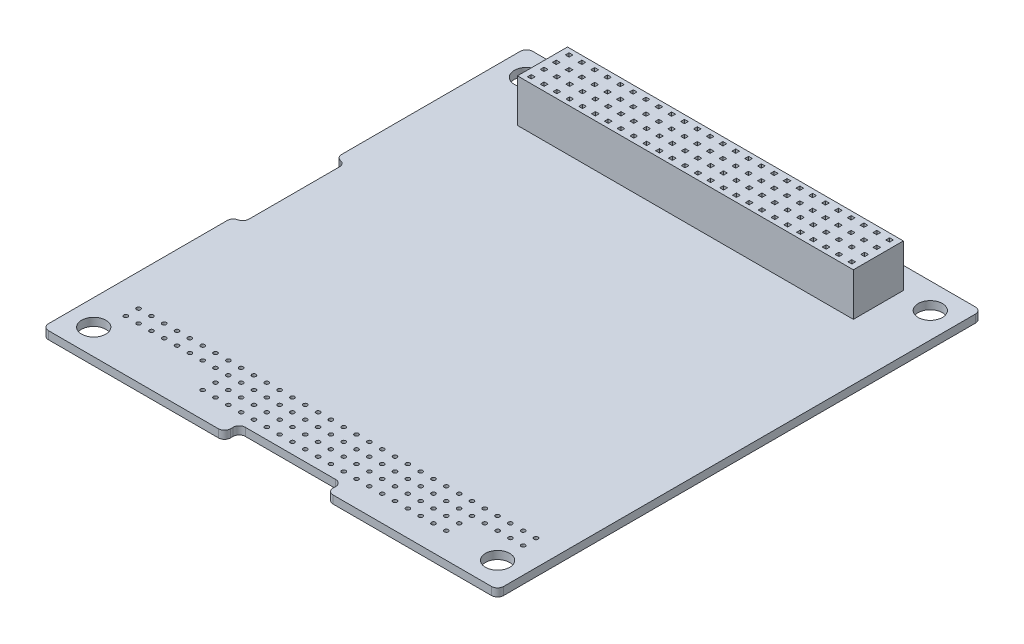
SolidWorks part; units mm, degrees
ref_plane "Front Plane" through (0, 0, 0) normal (0, 0, 1) x (1, 0, 0)
ref_plane "Top Plane" through (0, 0, 0) normal (0, 1, 0) x (1, 0, 0)
ref_plane "Right Plane" through (0, 0, 0) normal (1, 0, 0) x (0, 0, -1)
sketch "Sketch1" plane through (0, 0, 0) normal (0, 1, 0) x (1, 0, 0)
  line L1 (-45.085, -47.945) -> (45.085, -47.945)
  line L2 (-45.085, -47.945) -> (-45.085, 47.945)
  line L3 (-45.085, 47.945) -> (45.085, 47.945)
  line L4 (45.085, -47.945) -> (45.085, 47.945)
  line L5 (-45.085, -47.945) -> (45.085, 47.945) construction
  line L6 (-45.085, 47.945) -> (45.085, -47.945) construction
  point P0 (0, 0)
  dimension "D1" = 95.89
  dimension "D2" = 90.17
extrude "Boss-Extrude1" add sketch "Sketch1" along normal blind 1.57
sketch "Sketch2" plane through (0, 1.57, 0) normal (0, 1, 0) x (1, 0, 0)
  line L0 (-45.085, 47.945) -> (-9.015, 47.945) construction
  line L1 (45.085, 47.945) -> (-45.085, 47.945) construction
  line L2 (-45.085, -47.945) -> (-45.085, -10.135) construction
  line L3 (-9.015, 47.945) -> (11.305, 47.945)
  line L4 (-9.015, 47.945) -> (-9.015, 45.015)
  line L5 (-9.015, 45.015) -> (11.305, 45.015)
  line L6 (11.305, 47.945) -> (11.305, 45.015)
  line L7 (-45.085, 47.945) -> (-45.085, -47.945) construction
  line L8 (-45.085, -47.945) -> (-9.015, -47.945) construction
  line L9 (-45.085, -10.135) -> (-43.165, -10.135)
  line L10 (-45.085, -10.135) -> (-45.085, 10.135)
  line L11 (-45.085, 10.135) -> (-43.165, 10.135)
  line L12 (-43.165, -10.135) -> (-43.165, 10.135)
  line L13 (-45.085, -47.945) -> (45.085, -47.945) construction
  line L15 (-9.015, -47.945) -> (11.305, -47.945)
  line L16 (-9.015, -47.945) -> (-9.015, -45.025)
  line L17 (-9.015, -45.025) -> (11.305, -45.025)
  line L18 (11.305, -47.945) -> (11.305, -45.025)
  dimension "D1" = 36.07
  dimension "D2" = 20.32
  dimension "D3" = 2.93
  dimension "D4" = 37.81
  dimension "D5" = 20.27
  dimension "D6" = 1.92
  dimension "D7" = 2.92
extrude "Cut-Extrude1" cut sketch "Sketch2" against normal blind 1.57
sketch "Sketch3" plane through (0, 1.57, 0) normal (0, 1, 0) x (1, 0, 0)
  line L0 (-45.085, -47.945) -> (-40.005, -47.945) construction
  line L1 (-45.085, -47.945) -> (-9.015, -47.945) construction
  line L2 (-40.005, -47.945) -> (-40.005, -42.865) construction
  line L3 (45.085, -47.945) -> (40.005, -47.945) construction
  line L4 (11.305, -47.945) -> (45.085, -47.945) construction
  line L5 (40.005, -47.945) -> (40.005, -42.865) construction
  line L6 (-45.085, 47.945) -> (-40.005, 47.945) construction
  line L7 (-9.015, 47.945) -> (-45.085, 47.945) construction
  line L8 (-40.005, 47.945) -> (-40.005, 42.865) construction
  circle A0 centre (-40.005, -42.865) radius 2.4
  circle A1 centre (40.005, -42.865) radius 2.4
  circle A2 centre (-40.005, 42.865) radius 2.4
  circle A3 centre (40.005, 42.865) radius 2.4
  dimension "D3" = 4.8
  dimension "D6" = 5.08
  dimension "D4" = 5.08
  dimension "D5" = 4.8
  dimension "D7" = 4.8
  dimension "D8" = 4.8
  dimension "D1" = 5.08
  dimension "D2" = 5.08
extrude "Cut-Extrude2" cut sketch "Sketch3" against normal blind 1.57
sketch "Sketch4" plane through (0, 1.57, 0) normal (0, 1, 0) x (1, 0, 0)
  line L0 (-45.085, 47.945) -> (-45.085, 35.245) construction
  line L1 (-45.085, 47.945) -> (-45.085, 10.135) construction
  line L2 (-45.085, 35.245) -> (-31.115, 35.245) construction
  line L3 (-31.115, 35.245) -> (-32.639, 35.245)
  line L4 (-32.639, 35.245) -> (-32.639, 33.721) construction
  line L6 (-32.639, 33.721) -> (33.909, 33.721)
  line L7 (-32.639, 33.721) -> (-32.639, 43.627)
  line L8 (-32.639, 43.627) -> (33.909, 43.627)
  line L9 (33.909, 33.721) -> (33.909, 43.627)
  dimension "D1" = 12.7
  dimension "D2" = 13.97
  dimension "D3" = 1.524
  dimension "D4" = 1.524
  dimension "D5" = 9.906
  dimension "D6" = 66.548
extrude "Boss-Extrude3" add sketch "Sketch4" along normal blind 8.509 contours L6 L9 L8 L7 region at (0.635, 1.57, -38.674)
fillet "Fillet7" radius 1.2 1 edges at (-9.015, 0.785, 45.025)
fillet "Fillet8" radius 1.2 1 edges at (-9.015, 0.785, 47.945)
fillet "Fillet9" radius 1.2 2 edges at (11.305, 0.785, 47.945) (11.305, 0.785, 45.025)
fillet "Fillet10" radius 1.2 1 edges at (45.085, 0.785, 47.945)
fillet "Fillet11" radius 1.2 1 edges at (45.085, 0.785, -47.945)
fillet "Fillet12" radius 1.2 2 edges at (11.305, 0.785, -45.015) (11.305, 0.785, -47.945)
fillet "Fillet13" radius 1.2 2 edges at (-9.015, 0.785, -47.945) (-9.015, 0.785, -45.015)
fillet "Fillet14" radius 1.2 1 edges at (-45.085, 0.785, -47.945)
fillet "Fillet17" radius 1.2 1 edges at (-45.085, 0.785, -10.135)
fillet "Fillet18" radius 1.2 1 edges at (-43.165, 0.785, -10.135)
fillet "Fillet19" radius 1.2 1 edges at (-45.085, 0.785, 10.135)
fillet "Fillet20" radius 1.2 1 edges at (-43.165, 0.785, 10.135)
fillet "Fillet21" radius 1.2 1 edges at (-45.085, 0.785, 47.945)
sketch "Sketch7" plane through (0, 10.079, 0) normal (0, 1, 0) x (1, 0, 0)
  line L0 (-32.639, 33.721) -> (-31.115, 33.721) construction
  line L1 (-32.639, 33.721) -> (33.909, 33.721) construction
  line L2 (-31.115, 33.721) -> (-31.115, 34.9275) construction
  line L3 (-28.956, 34.5465) -> (-28.194, 34.5465)
  line L4 (-31.496, 34.5465) -> (-30.734, 34.5465)
  line L5 (-31.496, 34.5465) -> (-31.496, 35.3085)
  line L6 (-31.496, 35.3085) -> (-30.734, 35.3085)
  line L7 (-30.734, 34.5465) -> (-30.734, 35.3085)
  line L8 (-31.496, 34.5465) -> (-30.734, 35.3085) construction
  line L9 (-31.496, 35.3085) -> (-30.734, 34.5465) construction
  line L10 (-28.194, 34.5465) -> (-28.194, 35.3085)
  line L11 (-28.956, 35.3085) -> (-28.194, 35.3085)
  line L12 (-28.956, 34.5465) -> (-28.956, 35.3085)
  line L13 (-26.416, 34.5465) -> (-25.654, 34.5465)
  line L14 (-25.654, 34.5465) -> (-25.654, 35.3085)
  line L15 (-26.416, 35.3085) -> (-25.654, 35.3085)
  line L16 (-26.416, 34.5465) -> (-26.416, 35.3085)
  line L17 (-23.876, 34.5465) -> (-23.114, 34.5465)
  line L18 (-23.114, 34.5465) -> (-23.114, 35.3085)
  line L19 (-23.876, 35.3085) -> (-23.114, 35.3085)
  line L20 (-23.876, 34.5465) -> (-23.876, 35.3085)
  line L21 (-21.336, 34.5465) -> (-20.574, 34.5465)
  line L22 (-20.574, 34.5465) -> (-20.574, 35.3085)
  line L23 (-21.336, 35.3085) -> (-20.574, 35.3085)
  line L24 (-21.336, 34.5465) -> (-21.336, 35.3085)
  line L25 (-18.796, 34.5465) -> (-18.034, 34.5465)
  line L26 (-18.034, 34.5465) -> (-18.034, 35.3085)
  line L27 (-18.796, 35.3085) -> (-18.034, 35.3085)
  line L28 (-18.796, 34.5465) -> (-18.796, 35.3085)
  line L29 (-16.256, 34.5465) -> (-15.494, 34.5465)
  line L30 (-15.494, 34.5465) -> (-15.494, 35.3085)
  line L31 (-16.256, 35.3085) -> (-15.494, 35.3085)
  line L32 (-16.256, 34.5465) -> (-16.256, 35.3085)
  line L33 (-13.716, 34.5465) -> (-12.954, 34.5465)
  line L34 (-12.954, 34.5465) -> (-12.954, 35.3085)
  line L35 (-13.716, 35.3085) -> (-12.954, 35.3085)
  line L36 (-13.716, 34.5465) -> (-13.716, 35.3085)
  line L37 (-11.176, 34.5465) -> (-10.414, 34.5465)
  line L38 (-10.414, 34.5465) -> (-10.414, 35.3085)
  line L39 (-11.176, 35.3085) -> (-10.414, 35.3085)
  line L40 (-11.176, 34.5465) -> (-11.176, 35.3085)
  line L41 (-8.636, 34.5465) -> (-7.874, 34.5465)
  line L42 (-7.874, 34.5465) -> (-7.874, 35.3085)
  line L43 (-8.636, 35.3085) -> (-7.874, 35.3085)
  line L44 (-8.636, 34.5465) -> (-8.636, 35.3085)
  line L45 (-6.096, 34.5465) -> (-5.334, 34.5465)
  line L46 (-5.334, 34.5465) -> (-5.334, 35.3085)
  line L47 (-6.096, 35.3085) -> (-5.334, 35.3085)
  line L48 (-6.096, 34.5465) -> (-6.096, 35.3085)
  line L49 (-3.556, 34.5465) -> (-2.794, 34.5465)
  line L50 (-2.794, 34.5465) -> (-2.794, 35.3085)
  line L51 (-3.556, 35.3085) -> (-2.794, 35.3085)
  line L52 (-3.556, 34.5465) -> (-3.556, 35.3085)
  line L53 (-1.016, 34.5465) -> (-0.254, 34.5465)
  line L54 (-0.254, 34.5465) -> (-0.254, 35.3085)
  line L55 (-1.016, 35.3085) -> (-0.254, 35.3085)
  line L56 (-1.016, 34.5465) -> (-1.016, 35.3085)
  line L57 (1.524, 34.5465) -> (2.286, 34.5465)
  line L58 (2.286, 34.5465) -> (2.286, 35.3085)
  line L59 (1.524, 35.3085) -> (2.286, 35.3085)
  line L60 (1.524, 34.5465) -> (1.524, 35.3085)
  line L61 (4.064, 34.5465) -> (4.826, 34.5465)
  line L62 (4.826, 34.5465) -> (4.826, 35.3085)
  line L63 (4.064, 35.3085) -> (4.826, 35.3085)
  line L64 (4.064, 34.5465) -> (4.064, 35.3085)
  line L65 (6.604, 34.5465) -> (7.366, 34.5465)
  line L66 (7.366, 34.5465) -> (7.366, 35.3085)
  line L67 (6.604, 35.3085) -> (7.366, 35.3085)
  line L68 (6.604, 34.5465) -> (6.604, 35.3085)
  line L69 (9.144, 34.5465) -> (9.906, 34.5465)
  line L70 (9.906, 34.5465) -> (9.906, 35.3085)
  line L71 (9.144, 35.3085) -> (9.906, 35.3085)
  line L72 (9.144, 34.5465) -> (9.144, 35.3085)
  line L73 (11.684, 34.5465) -> (12.446, 34.5465)
  line L74 (12.446, 34.5465) -> (12.446, 35.3085)
  line L75 (11.684, 35.3085) -> (12.446, 35.3085)
  line L76 (11.684, 34.5465) -> (11.684, 35.3085)
  line L77 (14.224, 34.5465) -> (14.986, 34.5465)
  line L78 (14.986, 34.5465) -> (14.986, 35.3085)
  line L79 (14.224, 35.3085) -> (14.986, 35.3085)
  line L80 (14.224, 34.5465) -> (14.224, 35.3085)
  line L81 (16.764, 34.5465) -> (17.526, 34.5465)
  line L82 (17.526, 34.5465) -> (17.526, 35.3085)
  line L83 (16.764, 35.3085) -> (17.526, 35.3085)
  line L84 (16.764, 34.5465) -> (16.764, 35.3085)
  line L85 (19.304, 34.5465) -> (20.066, 34.5465)
  line L86 (20.066, 34.5465) -> (20.066, 35.3085)
  line L87 (19.304, 35.3085) -> (20.066, 35.3085)
  line L88 (19.304, 34.5465) -> (19.304, 35.3085)
  line L89 (21.844, 34.5465) -> (22.606, 34.5465)
  line L90 (22.606, 34.5465) -> (22.606, 35.3085)
  line L91 (21.844, 35.3085) -> (22.606, 35.3085)
  line L92 (21.844, 34.5465) -> (21.844, 35.3085)
  line L93 (24.384, 34.5465) -> (25.146, 34.5465)
  line L94 (25.146, 34.5465) -> (25.146, 35.3085)
  line L95 (24.384, 35.3085) -> (25.146, 35.3085)
  line L96 (24.384, 34.5465) -> (24.384, 35.3085)
  line L97 (26.924, 34.5465) -> (27.686, 34.5465)
  line L98 (27.686, 34.5465) -> (27.686, 35.3085)
  line L99 (26.924, 35.3085) -> (27.686, 35.3085)
  line L100 (26.924, 34.5465) -> (26.924, 35.3085)
  line L101 (29.464, 34.5465) -> (30.226, 34.5465)
  line L102 (30.226, 34.5465) -> (30.226, 35.3085)
  line L103 (29.464, 35.3085) -> (30.226, 35.3085)
  line L104 (29.464, 34.5465) -> (29.464, 35.3085)
  line L105 (32.004, 34.5465) -> (32.766, 34.5465)
  line L106 (32.766, 34.5465) -> (32.766, 35.3085)
  line L107 (32.004, 35.3085) -> (32.766, 35.3085)
  line L108 (32.004, 34.5465) -> (32.004, 35.3085)
  dimension "D1" = 1.524
  dimension "D2" = 1.2065
  dimension "D3" = 0.762
  dimension "D4" = 0.762
  dimension "D5" = 26
extrude "Cut-Extrude4" cut sketch "Sketch7" against normal blind 8.509
sketch "Sketch8" plane through (0, 10.079, 0) normal (0, 1, 0) x (1, 0, 0)
  line L0 (-31.496, 35.3085) -> (-30.734, 34.5465) construction
  line L1 (-31.496, 34.5465) -> (-30.734, 35.3085) construction
  line L2 (-31.115, 34.9275) -> (-31.115, 37.4675) construction
  line L3 (-28.194, 37.0865) -> (-28.956, 37.0865)
  line L4 (-30.734, 37.8485) -> (-31.496, 37.8485)
  line L5 (-30.734, 37.8485) -> (-30.734, 37.0865)
  line L6 (-30.734, 37.0865) -> (-31.496, 37.0865)
  line L7 (-31.496, 37.8485) -> (-31.496, 37.0865)
  line L8 (-30.734, 37.8485) -> (-31.496, 37.0865) construction
  line L9 (-30.734, 37.0865) -> (-31.496, 37.8485) construction
  line L10 (-28.956, 37.8485) -> (-28.956, 37.0865)
  line L11 (-28.194, 37.8485) -> (-28.956, 37.8485)
  line L12 (-28.194, 37.8485) -> (-28.194, 37.0865)
  line L13 (-25.654, 37.0865) -> (-26.416, 37.0865)
  line L14 (-26.416, 37.8485) -> (-26.416, 37.0865)
  line L15 (-25.654, 37.8485) -> (-26.416, 37.8485)
  line L16 (-25.654, 37.8485) -> (-25.654, 37.0865)
  line L17 (-23.114, 37.0865) -> (-23.876, 37.0865)
  line L18 (-23.876, 37.8485) -> (-23.876, 37.0865)
  line L19 (-23.114, 37.8485) -> (-23.876, 37.8485)
  line L20 (-23.114, 37.8485) -> (-23.114, 37.0865)
  line L21 (-20.574, 37.0865) -> (-21.336, 37.0865)
  line L22 (-21.336, 37.8485) -> (-21.336, 37.0865)
  line L23 (-20.574, 37.8485) -> (-21.336, 37.8485)
  line L24 (-20.574, 37.8485) -> (-20.574, 37.0865)
  line L25 (-18.034, 37.0865) -> (-18.796, 37.0865)
  line L26 (-18.796, 37.8485) -> (-18.796, 37.0865)
  line L27 (-18.034, 37.8485) -> (-18.796, 37.8485)
  line L28 (-18.034, 37.8485) -> (-18.034, 37.0865)
  line L29 (-15.494, 37.0865) -> (-16.256, 37.0865)
  line L30 (-16.256, 37.8485) -> (-16.256, 37.0865)
  line L31 (-15.494, 37.8485) -> (-16.256, 37.8485)
  line L32 (-15.494, 37.8485) -> (-15.494, 37.0865)
  line L33 (-12.954, 37.0865) -> (-13.716, 37.0865)
  line L34 (-13.716, 37.8485) -> (-13.716, 37.0865)
  line L35 (-12.954, 37.8485) -> (-13.716, 37.8485)
  line L36 (-12.954, 37.8485) -> (-12.954, 37.0865)
  line L37 (-10.414, 37.0865) -> (-11.176, 37.0865)
  line L38 (-11.176, 37.8485) -> (-11.176, 37.0865)
  line L39 (-10.414, 37.8485) -> (-11.176, 37.8485)
  line L40 (-10.414, 37.8485) -> (-10.414, 37.0865)
  line L41 (-7.874, 37.0865) -> (-8.636, 37.0865)
  line L42 (-8.636, 37.8485) -> (-8.636, 37.0865)
  line L43 (-7.874, 37.8485) -> (-8.636, 37.8485)
  line L44 (-7.874, 37.8485) -> (-7.874, 37.0865)
  line L45 (-5.334, 37.0865) -> (-6.096, 37.0865)
  line L46 (-6.096, 37.8485) -> (-6.096, 37.0865)
  line L47 (-5.334, 37.8485) -> (-6.096, 37.8485)
  line L48 (-5.334, 37.8485) -> (-5.334, 37.0865)
  line L49 (-2.794, 37.0865) -> (-3.556, 37.0865)
  line L50 (-3.556, 37.8485) -> (-3.556, 37.0865)
  line L51 (-2.794, 37.8485) -> (-3.556, 37.8485)
  line L52 (-2.794, 37.8485) -> (-2.794, 37.0865)
  line L53 (-0.254, 37.0865) -> (-1.016, 37.0865)
  line L54 (-1.016, 37.8485) -> (-1.016, 37.0865)
  line L55 (-0.254, 37.8485) -> (-1.016, 37.8485)
  line L56 (-0.254, 37.8485) -> (-0.254, 37.0865)
  line L57 (2.286, 37.0865) -> (1.524, 37.0865)
  line L58 (1.524, 37.8485) -> (1.524, 37.0865)
  line L59 (2.286, 37.8485) -> (1.524, 37.8485)
  line L60 (2.286, 37.8485) -> (2.286, 37.0865)
  line L61 (4.826, 37.0865) -> (4.064, 37.0865)
  line L62 (4.064, 37.8485) -> (4.064, 37.0865)
  line L63 (4.826, 37.8485) -> (4.064, 37.8485)
  line L64 (4.826, 37.8485) -> (4.826, 37.0865)
  line L65 (7.366, 37.0865) -> (6.604, 37.0865)
  line L66 (6.604, 37.8485) -> (6.604, 37.0865)
  line L67 (7.366, 37.8485) -> (6.604, 37.8485)
  line L68 (7.366, 37.8485) -> (7.366, 37.0865)
  line L69 (9.906, 37.0865) -> (9.144, 37.0865)
  line L70 (9.144, 37.8485) -> (9.144, 37.0865)
  line L71 (9.906, 37.8485) -> (9.144, 37.8485)
  line L72 (9.906, 37.8485) -> (9.906, 37.0865)
  line L73 (12.446, 37.0865) -> (11.684, 37.0865)
  line L74 (11.684, 37.8485) -> (11.684, 37.0865)
  line L75 (12.446, 37.8485) -> (11.684, 37.8485)
  line L76 (12.446, 37.8485) -> (12.446, 37.0865)
  line L77 (14.986, 37.0865) -> (14.224, 37.0865)
  line L78 (14.224, 37.8485) -> (14.224, 37.0865)
  line L79 (14.986, 37.8485) -> (14.224, 37.8485)
  line L80 (14.986, 37.8485) -> (14.986, 37.0865)
  line L81 (17.526, 37.0865) -> (16.764, 37.0865)
  line L82 (16.764, 37.8485) -> (16.764, 37.0865)
  line L83 (17.526, 37.8485) -> (16.764, 37.8485)
  line L84 (17.526, 37.8485) -> (17.526, 37.0865)
  line L85 (20.066, 37.0865) -> (19.304, 37.0865)
  line L86 (19.304, 37.8485) -> (19.304, 37.0865)
  line L87 (20.066, 37.8485) -> (19.304, 37.8485)
  line L88 (20.066, 37.8485) -> (20.066, 37.0865)
  line L89 (22.606, 37.0865) -> (21.844, 37.0865)
  line L90 (21.844, 37.8485) -> (21.844, 37.0865)
  line L91 (22.606, 37.8485) -> (21.844, 37.8485)
  line L92 (22.606, 37.8485) -> (22.606, 37.0865)
  line L93 (25.146, 37.0865) -> (24.384, 37.0865)
  line L94 (24.384, 37.8485) -> (24.384, 37.0865)
  line L95 (25.146, 37.8485) -> (24.384, 37.8485)
  line L96 (25.146, 37.8485) -> (25.146, 37.0865)
  line L97 (27.686, 37.0865) -> (26.924, 37.0865)
  line L98 (26.924, 37.8485) -> (26.924, 37.0865)
  line L99 (27.686, 37.8485) -> (26.924, 37.8485)
  line L100 (27.686, 37.8485) -> (27.686, 37.0865)
  line L101 (30.226, 37.0865) -> (29.464, 37.0865)
  line L102 (29.464, 37.8485) -> (29.464, 37.0865)
  line L103 (30.226, 37.8485) -> (29.464, 37.8485)
  line L104 (30.226, 37.8485) -> (30.226, 37.0865)
  line L105 (32.766, 37.0865) -> (32.004, 37.0865)
  line L106 (32.004, 37.8485) -> (32.004, 37.0865)
  line L107 (32.766, 37.8485) -> (32.004, 37.8485)
  line L108 (32.766, 37.8485) -> (32.766, 37.0865)
  dimension "D1" = 2.54
  dimension "D2" = 0.762
  dimension "D3" = 26
extrude "Cut-Extrude5" cut sketch "Sketch8" against normal blind 8.509
sketch "Sketch9" plane through (0, 10.079, 0) normal (0, 1, 0) x (1, 0, 0)
  line L0 (-31.496, 37.0865) -> (-30.734, 37.8485) construction
  line L1 (-30.734, 37.8485) -> (-30.734, 37.0865) construction
  line L2 (-30.734, 37.0865) -> (-31.496, 37.8485) construction
  line L3 (-31.496, 37.8485) -> (-31.115, 37.4675) construction
  line L4 (-31.115, 37.4675) -> (-31.115, 39.8805) construction
  line L5 (-28.956, 39.4995) -> (-28.194, 39.4995)
  line L6 (-31.496, 39.4995) -> (-30.734, 39.4995)
  line L7 (-31.496, 39.4995) -> (-31.496, 40.2615)
  line L8 (-31.496, 40.2615) -> (-30.734, 40.2615)
  line L9 (-30.734, 39.4995) -> (-30.734, 40.2615)
  line L10 (-31.496, 39.4995) -> (-30.734, 40.2615) construction
  line L11 (-31.496, 40.2615) -> (-30.734, 39.4995) construction
  line L12 (-28.194, 39.4995) -> (-28.194, 40.2615)
  line L13 (-28.956, 40.2615) -> (-28.194, 40.2615)
  line L14 (-28.956, 39.4995) -> (-28.956, 40.2615)
  line L15 (-26.416, 39.4995) -> (-25.654, 39.4995)
  line L16 (-25.654, 39.4995) -> (-25.654, 40.2615)
  line L17 (-26.416, 40.2615) -> (-25.654, 40.2615)
  line L18 (-26.416, 39.4995) -> (-26.416, 40.2615)
  line L19 (-23.876, 39.4995) -> (-23.114, 39.4995)
  line L20 (-23.114, 39.4995) -> (-23.114, 40.2615)
  line L21 (-23.876, 40.2615) -> (-23.114, 40.2615)
  line L22 (-23.876, 39.4995) -> (-23.876, 40.2615)
  line L23 (-21.336, 39.4995) -> (-20.574, 39.4995)
  line L24 (-20.574, 39.4995) -> (-20.574, 40.2615)
  line L25 (-21.336, 40.2615) -> (-20.574, 40.2615)
  line L26 (-21.336, 39.4995) -> (-21.336, 40.2615)
  line L27 (-18.796, 39.4995) -> (-18.034, 39.4995)
  line L28 (-18.034, 39.4995) -> (-18.034, 40.2615)
  line L29 (-18.796, 40.2615) -> (-18.034, 40.2615)
  line L30 (-18.796, 39.4995) -> (-18.796, 40.2615)
  line L31 (-16.256, 39.4995) -> (-15.494, 39.4995)
  line L32 (-15.494, 39.4995) -> (-15.494, 40.2615)
  line L33 (-16.256, 40.2615) -> (-15.494, 40.2615)
  line L34 (-16.256, 39.4995) -> (-16.256, 40.2615)
  line L35 (-13.716, 39.4995) -> (-12.954, 39.4995)
  line L36 (-12.954, 39.4995) -> (-12.954, 40.2615)
  line L37 (-13.716, 40.2615) -> (-12.954, 40.2615)
  line L38 (-13.716, 39.4995) -> (-13.716, 40.2615)
  line L39 (-11.176, 39.4995) -> (-10.414, 39.4995)
  line L40 (-10.414, 39.4995) -> (-10.414, 40.2615)
  line L41 (-11.176, 40.2615) -> (-10.414, 40.2615)
  line L42 (-11.176, 39.4995) -> (-11.176, 40.2615)
  line L43 (-8.636, 39.4995) -> (-7.874, 39.4995)
  line L44 (-7.874, 39.4995) -> (-7.874, 40.2615)
  line L45 (-8.636, 40.2615) -> (-7.874, 40.2615)
  line L46 (-8.636, 39.4995) -> (-8.636, 40.2615)
  line L47 (-6.096, 39.4995) -> (-5.334, 39.4995)
  line L48 (-5.334, 39.4995) -> (-5.334, 40.2615)
  line L49 (-6.096, 40.2615) -> (-5.334, 40.2615)
  line L50 (-6.096, 39.4995) -> (-6.096, 40.2615)
  line L51 (-3.556, 39.4995) -> (-2.794, 39.4995)
  line L52 (-2.794, 39.4995) -> (-2.794, 40.2615)
  line L53 (-3.556, 40.2615) -> (-2.794, 40.2615)
  line L54 (-3.556, 39.4995) -> (-3.556, 40.2615)
  line L55 (-1.016, 39.4995) -> (-0.254, 39.4995)
  line L56 (-0.254, 39.4995) -> (-0.254, 40.2615)
  line L57 (-1.016, 40.2615) -> (-0.254, 40.2615)
  line L58 (-1.016, 39.4995) -> (-1.016, 40.2615)
  line L59 (1.524, 39.4995) -> (2.286, 39.4995)
  line L60 (2.286, 39.4995) -> (2.286, 40.2615)
  line L61 (1.524, 40.2615) -> (2.286, 40.2615)
  line L62 (1.524, 39.4995) -> (1.524, 40.2615)
  line L63 (4.064, 39.4995) -> (4.826, 39.4995)
  line L64 (4.826, 39.4995) -> (4.826, 40.2615)
  line L65 (4.064, 40.2615) -> (4.826, 40.2615)
  line L66 (4.064, 39.4995) -> (4.064, 40.2615)
  line L67 (6.604, 39.4995) -> (7.366, 39.4995)
  line L68 (7.366, 39.4995) -> (7.366, 40.2615)
  line L69 (6.604, 40.2615) -> (7.366, 40.2615)
  line L70 (6.604, 39.4995) -> (6.604, 40.2615)
  line L71 (9.144, 39.4995) -> (9.906, 39.4995)
  line L72 (9.906, 39.4995) -> (9.906, 40.2615)
  line L73 (9.144, 40.2615) -> (9.906, 40.2615)
  line L74 (9.144, 39.4995) -> (9.144, 40.2615)
  line L75 (11.684, 39.4995) -> (12.446, 39.4995)
  line L76 (12.446, 39.4995) -> (12.446, 40.2615)
  line L77 (11.684, 40.2615) -> (12.446, 40.2615)
  line L78 (11.684, 39.4995) -> (11.684, 40.2615)
  line L79 (14.224, 39.4995) -> (14.986, 39.4995)
  line L80 (14.986, 39.4995) -> (14.986, 40.2615)
  line L81 (14.224, 40.2615) -> (14.986, 40.2615)
  line L82 (14.224, 39.4995) -> (14.224, 40.2615)
  line L83 (16.764, 39.4995) -> (17.526, 39.4995)
  line L84 (17.526, 39.4995) -> (17.526, 40.2615)
  line L85 (16.764, 40.2615) -> (17.526, 40.2615)
  line L86 (16.764, 39.4995) -> (16.764, 40.2615)
  line L87 (19.304, 39.4995) -> (20.066, 39.4995)
  line L88 (20.066, 39.4995) -> (20.066, 40.2615)
  line L89 (19.304, 40.2615) -> (20.066, 40.2615)
  line L90 (19.304, 39.4995) -> (19.304, 40.2615)
  line L91 (21.844, 39.4995) -> (22.606, 39.4995)
  line L92 (22.606, 39.4995) -> (22.606, 40.2615)
  line L93 (21.844, 40.2615) -> (22.606, 40.2615)
  line L94 (21.844, 39.4995) -> (21.844, 40.2615)
  line L95 (24.384, 39.4995) -> (25.146, 39.4995)
  line L96 (25.146, 39.4995) -> (25.146, 40.2615)
  line L97 (24.384, 40.2615) -> (25.146, 40.2615)
  line L98 (24.384, 39.4995) -> (24.384, 40.2615)
  line L99 (26.924, 39.4995) -> (27.686, 39.4995)
  line L100 (27.686, 39.4995) -> (27.686, 40.2615)
  line L101 (26.924, 40.2615) -> (27.686, 40.2615)
  line L102 (26.924, 39.4995) -> (26.924, 40.2615)
  line L103 (29.464, 39.4995) -> (30.226, 39.4995)
  line L104 (30.226, 39.4995) -> (30.226, 40.2615)
  line L105 (29.464, 40.2615) -> (30.226, 40.2615)
  line L106 (29.464, 39.4995) -> (29.464, 40.2615)
  line L107 (32.004, 39.4995) -> (32.766, 39.4995)
  line L108 (32.766, 39.4995) -> (32.766, 40.2615)
  line L109 (32.004, 40.2615) -> (32.766, 40.2615)
  line L110 (32.004, 39.4995) -> (32.004, 40.2615)
  dimension "D1" = 2.413
  dimension "D2" = 0.762
  dimension "D3" = 0.762
  dimension "D4" = 26
extrude "Cut-Extrude6" cut sketch "Sketch9" against normal blind 8.509
sketch "Sketch10" plane through (0, 10.079, 0) normal (0, 1, 0) x (1, 0, 0)
  line L0 (-30.734, 39.4995) -> (-31.496, 40.2615) construction
  line L1 (-31.496, 40.2615) -> (-31.496, 39.4995) construction
  line L2 (-31.496, 39.4995) -> (-30.734, 40.2615) construction
  line L3 (-30.734, 40.2615) -> (-31.115, 39.8805) construction
  line L4 (-31.115, 39.8805) -> (-31.115, 42.4205) construction
  line L5 (-28.194, 42.0395) -> (-28.194, 42.8015)
  line L6 (-31.496, 42.0395) -> (-30.734, 42.0395)
  line L7 (-31.496, 42.0395) -> (-31.496, 42.8015)
  line L8 (-31.496, 42.8015) -> (-30.734, 42.8015)
  line L9 (-30.734, 42.0395) -> (-30.734, 42.8015)
  line L10 (-31.496, 42.0395) -> (-30.734, 42.8015) construction
  line L11 (-31.496, 42.8015) -> (-30.734, 42.0395) construction
  line L12 (-28.956, 42.8015) -> (-28.194, 42.8015)
  line L13 (-28.956, 42.0395) -> (-28.956, 42.8015)
  line L14 (-28.956, 42.0395) -> (-28.194, 42.0395)
  line L15 (-25.654, 42.0395) -> (-25.654, 42.8015)
  line L16 (-26.416, 42.8015) -> (-25.654, 42.8015)
  line L17 (-26.416, 42.0395) -> (-26.416, 42.8015)
  line L18 (-26.416, 42.0395) -> (-25.654, 42.0395)
  line L19 (-23.114, 42.0395) -> (-23.114, 42.8015)
  line L20 (-23.876, 42.8015) -> (-23.114, 42.8015)
  line L21 (-23.876, 42.0395) -> (-23.876, 42.8015)
  line L22 (-23.876, 42.0395) -> (-23.114, 42.0395)
  line L23 (-20.574, 42.0395) -> (-20.574, 42.8015)
  line L24 (-21.336, 42.8015) -> (-20.574, 42.8015)
  line L25 (-21.336, 42.0395) -> (-21.336, 42.8015)
  line L26 (-21.336, 42.0395) -> (-20.574, 42.0395)
  line L27 (-18.034, 42.0395) -> (-18.034, 42.8015)
  line L28 (-18.796, 42.8015) -> (-18.034, 42.8015)
  line L29 (-18.796, 42.0395) -> (-18.796, 42.8015)
  line L30 (-18.796, 42.0395) -> (-18.034, 42.0395)
  line L31 (-15.494, 42.0395) -> (-15.494, 42.8015)
  line L32 (-16.256, 42.8015) -> (-15.494, 42.8015)
  line L33 (-16.256, 42.0395) -> (-16.256, 42.8015)
  line L34 (-16.256, 42.0395) -> (-15.494, 42.0395)
  line L35 (-12.954, 42.0395) -> (-12.954, 42.8015)
  line L36 (-13.716, 42.8015) -> (-12.954, 42.8015)
  line L37 (-13.716, 42.0395) -> (-13.716, 42.8015)
  line L38 (-13.716, 42.0395) -> (-12.954, 42.0395)
  line L39 (-10.414, 42.0395) -> (-10.414, 42.8015)
  line L40 (-11.176, 42.8015) -> (-10.414, 42.8015)
  line L41 (-11.176, 42.0395) -> (-11.176, 42.8015)
  line L42 (-11.176, 42.0395) -> (-10.414, 42.0395)
  line L43 (-7.874, 42.0395) -> (-7.874, 42.8015)
  line L44 (-8.636, 42.8015) -> (-7.874, 42.8015)
  line L45 (-8.636, 42.0395) -> (-8.636, 42.8015)
  line L46 (-8.636, 42.0395) -> (-7.874, 42.0395)
  line L47 (-5.334, 42.0395) -> (-5.334, 42.8015)
  line L48 (-6.096, 42.8015) -> (-5.334, 42.8015)
  line L49 (-6.096, 42.0395) -> (-6.096, 42.8015)
  line L50 (-6.096, 42.0395) -> (-5.334, 42.0395)
  line L51 (-2.794, 42.0395) -> (-2.794, 42.8015)
  line L52 (-3.556, 42.8015) -> (-2.794, 42.8015)
  line L53 (-3.556, 42.0395) -> (-3.556, 42.8015)
  line L54 (-3.556, 42.0395) -> (-2.794, 42.0395)
  line L55 (-0.254, 42.0395) -> (-0.254, 42.8015)
  line L56 (-1.016, 42.8015) -> (-0.254, 42.8015)
  line L57 (-1.016, 42.0395) -> (-1.016, 42.8015)
  line L58 (-1.016, 42.0395) -> (-0.254, 42.0395)
  line L59 (2.286, 42.0395) -> (2.286, 42.8015)
  line L60 (1.524, 42.8015) -> (2.286, 42.8015)
  line L61 (1.524, 42.0395) -> (1.524, 42.8015)
  line L62 (1.524, 42.0395) -> (2.286, 42.0395)
  line L63 (4.826, 42.0395) -> (4.826, 42.8015)
  line L64 (4.064, 42.8015) -> (4.826, 42.8015)
  line L65 (4.064, 42.0395) -> (4.064, 42.8015)
  line L66 (4.064, 42.0395) -> (4.826, 42.0395)
  line L67 (7.366, 42.0395) -> (7.366, 42.8015)
  line L68 (6.604, 42.8015) -> (7.366, 42.8015)
  line L69 (6.604, 42.0395) -> (6.604, 42.8015)
  line L70 (6.604, 42.0395) -> (7.366, 42.0395)
  line L71 (9.906, 42.0395) -> (9.906, 42.8015)
  line L72 (9.144, 42.8015) -> (9.906, 42.8015)
  line L73 (9.144, 42.0395) -> (9.144, 42.8015)
  line L74 (9.144, 42.0395) -> (9.906, 42.0395)
  line L75 (12.446, 42.0395) -> (12.446, 42.8015)
  line L76 (11.684, 42.8015) -> (12.446, 42.8015)
  line L77 (11.684, 42.0395) -> (11.684, 42.8015)
  line L78 (11.684, 42.0395) -> (12.446, 42.0395)
  line L79 (14.986, 42.0395) -> (14.986, 42.8015)
  line L80 (14.224, 42.8015) -> (14.986, 42.8015)
  line L81 (14.224, 42.0395) -> (14.224, 42.8015)
  line L82 (14.224, 42.0395) -> (14.986, 42.0395)
  line L83 (17.526, 42.0395) -> (17.526, 42.8015)
  line L84 (16.764, 42.8015) -> (17.526, 42.8015)
  line L85 (16.764, 42.0395) -> (16.764, 42.8015)
  line L86 (16.764, 42.0395) -> (17.526, 42.0395)
  line L87 (20.066, 42.0395) -> (20.066, 42.8015)
  line L88 (19.304, 42.8015) -> (20.066, 42.8015)
  line L89 (19.304, 42.0395) -> (19.304, 42.8015)
  line L90 (19.304, 42.0395) -> (20.066, 42.0395)
  line L91 (22.606, 42.0395) -> (22.606, 42.8015)
  line L92 (21.844, 42.8015) -> (22.606, 42.8015)
  line L93 (21.844, 42.0395) -> (21.844, 42.8015)
  line L94 (21.844, 42.0395) -> (22.606, 42.0395)
  line L95 (25.146, 42.0395) -> (25.146, 42.8015)
  line L96 (24.384, 42.8015) -> (25.146, 42.8015)
  line L97 (24.384, 42.0395) -> (24.384, 42.8015)
  line L98 (24.384, 42.0395) -> (25.146, 42.0395)
  line L99 (27.686, 42.0395) -> (27.686, 42.8015)
  line L100 (26.924, 42.8015) -> (27.686, 42.8015)
  line L101 (26.924, 42.0395) -> (26.924, 42.8015)
  line L102 (26.924, 42.0395) -> (27.686, 42.0395)
  line L103 (30.226, 42.0395) -> (30.226, 42.8015)
  line L104 (29.464, 42.8015) -> (30.226, 42.8015)
  line L105 (29.464, 42.0395) -> (29.464, 42.8015)
  line L106 (29.464, 42.0395) -> (30.226, 42.0395)
  line L107 (32.766, 42.0395) -> (32.766, 42.8015)
  line L108 (32.004, 42.8015) -> (32.766, 42.8015)
  line L109 (32.004, 42.0395) -> (32.004, 42.8015)
  line L110 (32.004, 42.0395) -> (32.766, 42.0395)
  dimension "D1" = 2.54
  dimension "D2" = 0.762
  dimension "D3" = 0.762
  dimension "D4" = 26
extrude "Cut-Extrude7" cut sketch "Sketch10" against normal blind 8.509
sketch "Sketch11" plane through (0, 1.57, 0) normal (0, 1, 0) x (1, 0, 0)
  line L0 (-43.885, -47.945) -> (-45.2926, -47.945) construction
  line L1 (-45.085, -46.745) -> (-45.085, -47.945) construction
  line L2 (-45.085, -47.945) -> (-38.735, -47.945) construction
  line L3 (-43.885, -47.945) -> (-10.215, -47.945) construction
  line L4 (-38.735, -47.945) -> (-38.735, -37.785) construction
  circle A0 centre (-38.735, -37.785) radius 0.4
  circle A1 centre (-36.195, -37.785) radius 0.4
  circle A2 centre (-33.655, -37.785) radius 0.4
  circle A3 centre (-31.115, -37.785) radius 0.4
  circle A4 centre (-28.575, -37.785) radius 0.4
  circle A5 centre (-26.035, -37.785) radius 0.4
  circle A6 centre (-23.495, -37.785) radius 0.4
  circle A7 centre (-20.955, -37.785) radius 0.4
  circle A8 centre (-18.415, -37.785) radius 0.4
  circle A9 centre (-15.875, -37.785) radius 0.4
  circle A10 centre (-13.335, -37.785) radius 0.4
  circle A11 centre (-10.795, -37.785) radius 0.4
  circle A12 centre (-8.255, -37.785) radius 0.4
  circle A13 centre (-5.715, -37.785) radius 0.4
  circle A14 centre (-3.175, -37.785) radius 0.4
  circle A15 centre (-0.635, -37.785) radius 0.4
  circle A16 centre (1.905, -37.785) radius 0.4
  circle A17 centre (4.445, -37.785) radius 0.4
  circle A18 centre (6.985, -37.785) radius 0.4
  circle A19 centre (9.525, -37.785) radius 0.4
  circle A20 centre (12.065, -37.785) radius 0.4
  circle A21 centre (14.605, -37.785) radius 0.4
  circle A22 centre (17.145, -37.785) radius 0.4
  circle A23 centre (19.685, -37.785) radius 0.4
  circle A24 centre (22.225, -37.785) radius 0.4
  circle A25 centre (24.765, -37.785) radius 0.4
  circle A26 centre (27.305, -37.785) radius 0.4
  circle A27 centre (29.845, -37.785) radius 0.4
  circle A28 centre (32.385, -37.785) radius 0.4
  circle A29 centre (34.925, -37.785) radius 0.4
  circle A30 centre (37.465, -37.785) radius 0.4
  circle A31 centre (40.005, -37.785) radius 0.4
  dimension "D3" = 0.8
  dimension "D1" = 6.35
  dimension "D2" = 10.16
  dimension "D4" = 32
extrude "Cut-Extrude8" cut sketch "Sketch11" against normal blind 10
sketch "Sketch12" plane through (0, 1.57, 0) normal (0, 1, 0) x (1, 0, 0)
  line L0 (-38.735, -37.785) -> (-38.735, -35.245) construction
  circle A0 centre (-38.735, -35.245) radius 0.4
  circle A1 centre (-36.195, -35.245) radius 0.4
  circle A2 centre (-33.655, -35.245) radius 0.4
  circle A3 centre (-31.115, -35.245) radius 0.4
  circle A4 centre (-28.575, -35.245) radius 0.4
  circle A5 centre (-26.035, -35.245) radius 0.4
  circle A6 centre (-23.495, -35.245) radius 0.4
  circle A7 centre (-20.955, -35.245) radius 0.4
  circle A8 centre (-18.415, -35.245) radius 0.4
  circle A9 centre (-15.875, -35.245) radius 0.4
  circle A10 centre (-13.335, -35.245) radius 0.4
  circle A11 centre (-10.795, -35.245) radius 0.4
  circle A12 centre (-8.255, -35.245) radius 0.4
  circle A13 centre (-5.715, -35.245) radius 0.4
  circle A14 centre (-3.175, -35.245) radius 0.4
  circle A15 centre (-0.635, -35.245) radius 0.4
  circle A16 centre (1.905, -35.245) radius 0.4
  circle A17 centre (4.445, -35.245) radius 0.4
  circle A18 centre (6.985, -35.245) radius 0.4
  circle A19 centre (9.525, -35.245) radius 0.4
  circle A20 centre (12.065, -35.245) radius 0.4
  circle A21 centre (14.605, -35.245) radius 0.4
  circle A22 centre (17.145, -35.245) radius 0.4
  circle A23 centre (19.685, -35.245) radius 0.4
  circle A24 centre (22.225, -35.245) radius 0.4
  circle A25 centre (24.765, -35.245) radius 0.4
  circle A26 centre (27.305, -35.245) radius 0.4
  circle A27 centre (29.845, -35.245) radius 0.4
  circle A28 centre (32.385, -35.245) radius 0.4
  circle A29 centre (34.925, -35.245) radius 0.4
  circle A30 centre (37.465, -35.245) radius 0.4
  circle A31 centre (40.005, -35.245) radius 0.4
  dimension "D2" = 0.8
  dimension "D1" = 2.54
  dimension "D3" = 32
extrude "Cut-Extrude9" cut sketch "Sketch12" against normal blind 10
sketch "Sketch13" plane through (0, 1.57, 0) normal (0, 1, 0) x (1, 0, 0)
  line L0 (-43.885, -47.945) -> (-45.085, -47.945) construction
  line L1 (-45.085, -47.945) -> (-45.085, -46.745) construction
  line L2 (-45.085, -47.945) -> (-18.415, -47.945) construction
  line L3 (-43.885, -47.945) -> (-10.215, -47.945) construction
  line L4 (-18.415, -47.945) -> (-18.415, -42.865) construction
  circle A0 centre (-18.415, -42.865) radius 0.4
  circle A1 centre (-15.875, -42.865) radius 0.4
  circle A2 centre (-13.335, -42.865) radius 0.4
  circle A3 centre (-10.795, -42.865) radius 0.4
  circle A4 centre (-8.255, -42.865) radius 0.4
  circle A5 centre (-5.715, -42.865) radius 0.4
  circle A6 centre (-3.175, -42.865) radius 0.4
  circle A7 centre (-0.635, -42.865) radius 0.4
  circle A8 centre (1.905, -42.865) radius 0.4
  circle A9 centre (4.445, -42.865) radius 0.4
  circle A10 centre (6.985, -42.865) radius 0.4
  circle A11 centre (9.525, -42.865) radius 0.4
  circle A12 centre (12.065, -42.865) radius 0.4
  circle A13 centre (14.605, -42.865) radius 0.4
  circle A14 centre (17.145, -42.865) radius 0.4
  circle A15 centre (19.685, -42.865) radius 0.4
  circle A16 centre (22.225, -42.865) radius 0.4
  circle A17 centre (24.765, -42.865) radius 0.4
  circle A18 centre (27.305, -42.865) radius 0.4
  circle A19 centre (29.845, -42.865) radius 0.4
  dimension "D3" = 0.8
  dimension "D1" = 26.67
  dimension "D2" = 5.08
  dimension "D4" = 20
extrude "Cut-Extrude10" cut sketch "Sketch13" against normal blind 10
sketch "Sketch14" plane through (0, 1.57, 0) normal (0, 1, 0) x (1, 0, 0)
  line L0 (-18.415, -42.865) -> (-18.415, -40.325) construction
  circle A0 centre (-18.415, -40.325) radius 0.4
  circle A1 centre (-15.875, -40.325) radius 0.4
  circle A2 centre (-13.335, -40.325) radius 0.4
  circle A3 centre (-10.795, -40.325) radius 0.4
  circle A4 centre (-8.255, -40.325) radius 0.4
  circle A5 centre (-5.715, -40.325) radius 0.4
  circle A6 centre (-3.175, -40.325) radius 0.4
  circle A7 centre (-0.635, -40.325) radius 0.4
  circle A8 centre (1.905, -40.325) radius 0.4
  circle A9 centre (4.445, -40.325) radius 0.4
  circle A10 centre (6.985, -40.325) radius 0.4
  circle A11 centre (9.525, -40.325) radius 0.4
  circle A12 centre (12.065, -40.325) radius 0.4
  circle A13 centre (14.605, -40.325) radius 0.4
  circle A14 centre (17.145, -40.325) radius 0.4
  circle A15 centre (19.685, -40.325) radius 0.4
  circle A16 centre (22.225, -40.325) radius 0.4
  circle A17 centre (24.765, -40.325) radius 0.4
  circle A18 centre (27.305, -40.325) radius 0.4
  circle A19 centre (29.845, -40.325) radius 0.4
  dimension "D2" = 0.8
  dimension "D1" = 2.54
  dimension "D3" = 20
extrude "Cut-Extrude11" cut sketch "Sketch14" against normal blind 10
sketch "Sketch15" plane through (0, 0, 0) normal (0, -1, 0) x (1, 0, 0)
  line L0 (-28.2575, -42.738) -> (-28.2575, -42.103)
  line L1 (-31.4325, -42.738) -> (-30.7975, -42.738)
  line L2 (-31.4325, -42.738) -> (-31.4325, -42.103)
  line L3 (-28.8925, -42.738) -> (-28.2575, -42.738)
  line L4 (-31.4325, -42.103) -> (-30.7975, -42.103)
  line L5 (-28.8925, -42.103) -> (-28.2575, -42.103)
  line L6 (-31.115, -42.4205) -> (-28.575, -42.4205) construction
  line L7 (-30.7975, -42.738) -> (-30.7975, -42.103)
  line L8 (-31.4325, -42.738) -> (-30.7975, -42.103) construction
  line L9 (-31.4325, -42.103) -> (-30.7975, -42.738) construction
  line L10 (-28.8925, -42.738) -> (-28.8925, -42.103)
  line L11 (-25.7175, -42.738) -> (-25.7175, -42.103)
  line L12 (-26.3525, -42.738) -> (-25.7175, -42.738)
  line L13 (-26.3525, -42.103) -> (-25.7175, -42.103)
  line L14 (-26.3525, -42.738) -> (-26.3525, -42.103)
  line L15 (-23.1775, -42.738) -> (-23.1775, -42.103)
  line L16 (-23.8125, -42.738) -> (-23.1775, -42.738)
  line L17 (-23.8125, -42.103) -> (-23.1775, -42.103)
  line L18 (-23.8125, -42.738) -> (-23.8125, -42.103)
  line L19 (-20.6375, -42.738) -> (-20.6375, -42.103)
  line L20 (-21.2725, -42.738) -> (-20.6375, -42.738)
  line L21 (-21.2725, -42.103) -> (-20.6375, -42.103)
  line L22 (-21.2725, -42.738) -> (-21.2725, -42.103)
  line L23 (-18.0975, -42.738) -> (-18.0975, -42.103)
  line L24 (-18.7325, -42.738) -> (-18.0975, -42.738)
  line L25 (-18.7325, -42.103) -> (-18.0975, -42.103)
  line L26 (-18.7325, -42.738) -> (-18.7325, -42.103)
  line L27 (-15.5575, -42.738) -> (-15.5575, -42.103)
  line L28 (-16.1925, -42.738) -> (-15.5575, -42.738)
  line L29 (-16.1925, -42.103) -> (-15.5575, -42.103)
  line L30 (-16.1925, -42.738) -> (-16.1925, -42.103)
  line L31 (-13.0175, -42.738) -> (-13.0175, -42.103)
  line L32 (-13.6525, -42.738) -> (-13.0175, -42.738)
  line L33 (-13.6525, -42.103) -> (-13.0175, -42.103)
  line L34 (-13.6525, -42.738) -> (-13.6525, -42.103)
  line L35 (-10.4775, -42.738) -> (-10.4775, -42.103)
  line L36 (-11.1125, -42.738) -> (-10.4775, -42.738)
  line L37 (-11.1125, -42.103) -> (-10.4775, -42.103)
  line L38 (-11.1125, -42.738) -> (-11.1125, -42.103)
  line L39 (-7.9375, -42.738) -> (-7.9375, -42.103)
  line L40 (-8.5725, -42.738) -> (-7.9375, -42.738)
  line L41 (-8.5725, -42.103) -> (-7.9375, -42.103)
  line L42 (-8.5725, -42.738) -> (-8.5725, -42.103)
  line L43 (-5.3975, -42.738) -> (-5.3975, -42.103)
  line L44 (-6.0325, -42.738) -> (-5.3975, -42.738)
  line L45 (-6.0325, -42.103) -> (-5.3975, -42.103)
  line L46 (-6.0325, -42.738) -> (-6.0325, -42.103)
  line L47 (-2.8575, -42.738) -> (-2.8575, -42.103)
  line L48 (-3.4925, -42.738) -> (-2.8575, -42.738)
  line L49 (-3.4925, -42.103) -> (-2.8575, -42.103)
  line L50 (-3.4925, -42.738) -> (-3.4925, -42.103)
  line L51 (-0.3175, -42.738) -> (-0.3175, -42.103)
  line L52 (-0.9525, -42.738) -> (-0.3175, -42.738)
  line L53 (-0.9525, -42.103) -> (-0.3175, -42.103)
  line L54 (-0.9525, -42.738) -> (-0.9525, -42.103)
  line L55 (2.2225, -42.738) -> (2.2225, -42.103)
  line L56 (1.5875, -42.738) -> (2.2225, -42.738)
  line L57 (1.5875, -42.103) -> (2.2225, -42.103)
  line L58 (1.5875, -42.738) -> (1.5875, -42.103)
  line L59 (4.7625, -42.738) -> (4.7625, -42.103)
  line L60 (4.1275, -42.738) -> (4.7625, -42.738)
  line L61 (4.1275, -42.103) -> (4.7625, -42.103)
  line L62 (4.1275, -42.738) -> (4.1275, -42.103)
  line L63 (7.3025, -42.738) -> (7.3025, -42.103)
  line L64 (6.6675, -42.738) -> (7.3025, -42.738)
  line L65 (6.6675, -42.103) -> (7.3025, -42.103)
  line L66 (6.6675, -42.738) -> (6.6675, -42.103)
  line L67 (9.8425, -42.738) -> (9.8425, -42.103)
  line L68 (9.2075, -42.738) -> (9.8425, -42.738)
  line L69 (9.2075, -42.103) -> (9.8425, -42.103)
  line L70 (9.2075, -42.738) -> (9.2075, -42.103)
  line L71 (12.3825, -42.738) -> (12.3825, -42.103)
  line L72 (11.7475, -42.738) -> (12.3825, -42.738)
  line L73 (11.7475, -42.103) -> (12.3825, -42.103)
  line L74 (11.7475, -42.738) -> (11.7475, -42.103)
  line L75 (14.9225, -42.738) -> (14.9225, -42.103)
  line L76 (14.2875, -42.738) -> (14.9225, -42.738)
  line L77 (14.2875, -42.103) -> (14.9225, -42.103)
  line L78 (14.2875, -42.738) -> (14.2875, -42.103)
  line L79 (17.4625, -42.738) -> (17.4625, -42.103)
  line L80 (16.8275, -42.738) -> (17.4625, -42.738)
  line L81 (16.8275, -42.103) -> (17.4625, -42.103)
  line L82 (16.8275, -42.738) -> (16.8275, -42.103)
  line L83 (20.0025, -42.738) -> (20.0025, -42.103)
  line L84 (19.3675, -42.738) -> (20.0025, -42.738)
  line L85 (19.3675, -42.103) -> (20.0025, -42.103)
  line L86 (19.3675, -42.738) -> (19.3675, -42.103)
  line L87 (22.5425, -42.738) -> (22.5425, -42.103)
  line L88 (21.9075, -42.738) -> (22.5425, -42.738)
  line L89 (21.9075, -42.103) -> (22.5425, -42.103)
  line L90 (21.9075, -42.738) -> (21.9075, -42.103)
  line L91 (25.0825, -42.738) -> (25.0825, -42.103)
  line L92 (24.4475, -42.738) -> (25.0825, -42.738)
  line L93 (24.4475, -42.103) -> (25.0825, -42.103)
  line L94 (24.4475, -42.738) -> (24.4475, -42.103)
  line L95 (27.6225, -42.738) -> (27.6225, -42.103)
  line L96 (26.9875, -42.738) -> (27.6225, -42.738)
  line L97 (26.9875, -42.103) -> (27.6225, -42.103)
  line L98 (26.9875, -42.738) -> (26.9875, -42.103)
  line L99 (30.1625, -42.738) -> (30.1625, -42.103)
  line L100 (29.5275, -42.738) -> (30.1625, -42.738)
  line L101 (29.5275, -42.103) -> (30.1625, -42.103)
  line L102 (29.5275, -42.738) -> (29.5275, -42.103)
  line L103 (32.7025, -42.738) -> (32.7025, -42.103)
  line L104 (32.0675, -42.738) -> (32.7025, -42.738)
  line L105 (32.0675, -42.103) -> (32.7025, -42.103)
  line L106 (32.0675, -42.738) -> (32.0675, -42.103)
  dimension "D1" = 0.635
  dimension "D2" = 0.635
  dimension "D3" = 26
extrude "Boss-Extrude4" add sketch "Sketch15" along normal blind 12.2
sketch "Sketch16" plane through (0, 0, 0) normal (0, -1, 0) x (1, 0, 0)
  line L0 (-31.4325, -42.738) -> (-30.7975, -42.103) construction
  line L1 (-30.7975, -42.738) -> (-31.4325, -42.103) construction
  line L2 (-31.115, -42.4205) -> (-31.115, -39.8805) construction
  line L3 (-31.115, -39.8805) -> (-31.115, -37.3405) construction
  line L4 (-31.4325, -40.198) -> (-30.7975, -40.198)
  line L5 (-31.4325, -40.198) -> (-31.4325, -39.563)
  line L6 (-31.4325, -39.563) -> (-30.7975, -39.563)
  line L7 (-30.7975, -40.198) -> (-30.7975, -39.563)
  line L8 (-31.4325, -40.198) -> (-30.7975, -39.563) construction
  line L9 (-31.4325, -39.563) -> (-30.7975, -40.198) construction
  line L10 (-31.115, -37.3405) -> (-31.115, -34.8005) construction
  line L11 (-30.7975, -37.658) -> (-31.4325, -37.658)
  line L12 (-30.7975, -37.658) -> (-30.7975, -37.023)
  line L13 (-30.7975, -37.023) -> (-31.4325, -37.023)
  line L14 (-31.4325, -37.658) -> (-31.4325, -37.023)
  line L15 (-30.7975, -37.658) -> (-31.4325, -37.023) construction
  line L16 (-30.7975, -37.023) -> (-31.4325, -37.658) construction
  line L17 (-28.8925, -40.198) -> (-28.2575, -40.198)
  line L18 (-30.7975, -35.118) -> (-31.4325, -35.118)
  line L19 (-30.7975, -35.118) -> (-30.7975, -34.483)
  line L20 (-30.7975, -34.483) -> (-31.4325, -34.483)
  line L21 (-31.4325, -35.118) -> (-31.4325, -34.483)
  line L22 (-30.7975, -35.118) -> (-31.4325, -34.483) construction
  line L23 (-30.7975, -34.483) -> (-31.4325, -35.118) construction
  line L24 (-28.2575, -40.198) -> (-28.2575, -39.563)
  line L25 (-28.8925, -39.563) -> (-28.2575, -39.563)
  line L26 (-28.8925, -40.198) -> (-28.8925, -39.563)
  line L27 (-28.2575, -37.658) -> (-28.8925, -37.658)
  line L28 (-28.2575, -37.658) -> (-28.2575, -37.023)
  line L29 (-28.8925, -37.658) -> (-28.8925, -37.023)
  line L30 (-28.2575, -37.023) -> (-28.8925, -37.023)
  line L31 (-28.2575, -35.118) -> (-28.8925, -35.118)
  line L32 (-28.2575, -35.118) -> (-28.2575, -34.483)
  line L33 (-28.2575, -34.483) -> (-28.8925, -34.483)
  line L34 (-28.8925, -35.118) -> (-28.8925, -34.483)
  line L35 (-26.3525, -40.198) -> (-25.7175, -40.198)
  line L36 (-25.7175, -40.198) -> (-25.7175, -39.563)
  line L37 (-26.3525, -39.563) -> (-25.7175, -39.563)
  line L38 (-26.3525, -40.198) -> (-26.3525, -39.563)
  line L39 (-25.7175, -37.658) -> (-26.3525, -37.658)
  line L40 (-25.7175, -37.658) -> (-25.7175, -37.023)
  line L41 (-26.3525, -37.658) -> (-26.3525, -37.023)
  line L42 (-25.7175, -37.023) -> (-26.3525, -37.023)
  line L43 (-25.7175, -35.118) -> (-26.3525, -35.118)
  line L44 (-25.7175, -35.118) -> (-25.7175, -34.483)
  line L45 (-25.7175, -34.483) -> (-26.3525, -34.483)
  line L46 (-26.3525, -35.118) -> (-26.3525, -34.483)
  line L47 (-23.8125, -40.198) -> (-23.1775, -40.198)
  line L48 (-23.1775, -40.198) -> (-23.1775, -39.563)
  line L49 (-23.8125, -39.563) -> (-23.1775, -39.563)
  line L50 (-23.8125, -40.198) -> (-23.8125, -39.563)
  line L51 (-23.1775, -37.658) -> (-23.8125, -37.658)
  line L52 (-23.1775, -37.658) -> (-23.1775, -37.023)
  line L53 (-23.8125, -37.658) -> (-23.8125, -37.023)
  line L54 (-23.1775, -37.023) -> (-23.8125, -37.023)
  line L55 (-23.1775, -35.118) -> (-23.8125, -35.118)
  line L56 (-23.1775, -35.118) -> (-23.1775, -34.483)
  line L57 (-23.1775, -34.483) -> (-23.8125, -34.483)
  line L58 (-23.8125, -35.118) -> (-23.8125, -34.483)
  line L59 (-21.2725, -40.198) -> (-20.6375, -40.198)
  line L60 (-20.6375, -40.198) -> (-20.6375, -39.563)
  line L61 (-21.2725, -39.563) -> (-20.6375, -39.563)
  line L62 (-21.2725, -40.198) -> (-21.2725, -39.563)
  line L63 (-20.6375, -37.658) -> (-21.2725, -37.658)
  line L64 (-20.6375, -37.658) -> (-20.6375, -37.023)
  line L65 (-21.2725, -37.658) -> (-21.2725, -37.023)
  line L66 (-20.6375, -37.023) -> (-21.2725, -37.023)
  line L67 (-20.6375, -35.118) -> (-21.2725, -35.118)
  line L68 (-20.6375, -35.118) -> (-20.6375, -34.483)
  line L69 (-20.6375, -34.483) -> (-21.2725, -34.483)
  line L70 (-21.2725, -35.118) -> (-21.2725, -34.483)
  line L71 (-18.7325, -40.198) -> (-18.0975, -40.198)
  line L72 (-18.0975, -40.198) -> (-18.0975, -39.563)
  line L73 (-18.7325, -39.563) -> (-18.0975, -39.563)
  line L74 (-18.7325, -40.198) -> (-18.7325, -39.563)
  line L75 (-18.0975, -37.658) -> (-18.7325, -37.658)
  line L76 (-18.0975, -37.658) -> (-18.0975, -37.023)
  line L77 (-18.7325, -37.658) -> (-18.7325, -37.023)
  line L78 (-18.0975, -37.023) -> (-18.7325, -37.023)
  line L79 (-18.0975, -35.118) -> (-18.7325, -35.118)
  line L80 (-18.0975, -35.118) -> (-18.0975, -34.483)
  line L81 (-18.0975, -34.483) -> (-18.7325, -34.483)
  line L82 (-18.7325, -35.118) -> (-18.7325, -34.483)
  line L83 (-16.1925, -40.198) -> (-15.5575, -40.198)
  line L84 (-15.5575, -40.198) -> (-15.5575, -39.563)
  line L85 (-16.1925, -39.563) -> (-15.5575, -39.563)
  line L86 (-16.1925, -40.198) -> (-16.1925, -39.563)
  line L87 (-15.5575, -37.658) -> (-16.1925, -37.658)
  line L88 (-15.5575, -37.658) -> (-15.5575, -37.023)
  line L89 (-16.1925, -37.658) -> (-16.1925, -37.023)
  line L90 (-15.5575, -37.023) -> (-16.1925, -37.023)
  line L91 (-15.5575, -35.118) -> (-16.1925, -35.118)
  line L92 (-15.5575, -35.118) -> (-15.5575, -34.483)
  line L93 (-15.5575, -34.483) -> (-16.1925, -34.483)
  line L94 (-16.1925, -35.118) -> (-16.1925, -34.483)
  line L95 (-13.6525, -40.198) -> (-13.0175, -40.198)
  line L96 (-13.0175, -40.198) -> (-13.0175, -39.563)
  line L97 (-13.6525, -39.563) -> (-13.0175, -39.563)
  line L98 (-13.6525, -40.198) -> (-13.6525, -39.563)
  line L99 (-13.0175, -37.658) -> (-13.6525, -37.658)
  line L100 (-13.0175, -37.658) -> (-13.0175, -37.023)
  line L101 (-13.6525, -37.658) -> (-13.6525, -37.023)
  line L102 (-13.0175, -37.023) -> (-13.6525, -37.023)
  line L103 (-13.0175, -35.118) -> (-13.6525, -35.118)
  line L104 (-13.0175, -35.118) -> (-13.0175, -34.483)
  line L105 (-13.0175, -34.483) -> (-13.6525, -34.483)
  line L106 (-13.6525, -35.118) -> (-13.6525, -34.483)
  line L107 (-11.1125, -40.198) -> (-10.4775, -40.198)
  line L108 (-10.4775, -40.198) -> (-10.4775, -39.563)
  line L109 (-11.1125, -39.563) -> (-10.4775, -39.563)
  line L110 (-11.1125, -40.198) -> (-11.1125, -39.563)
  line L111 (-10.4775, -37.658) -> (-11.1125, -37.658)
  line L112 (-10.4775, -37.658) -> (-10.4775, -37.023)
  line L113 (-11.1125, -37.658) -> (-11.1125, -37.023)
  line L114 (-10.4775, -37.023) -> (-11.1125, -37.023)
  line L115 (-10.4775, -35.118) -> (-11.1125, -35.118)
  line L116 (-10.4775, -35.118) -> (-10.4775, -34.483)
  line L117 (-10.4775, -34.483) -> (-11.1125, -34.483)
  line L118 (-11.1125, -35.118) -> (-11.1125, -34.483)
  line L119 (-8.5725, -40.198) -> (-7.9375, -40.198)
  line L120 (-7.9375, -40.198) -> (-7.9375, -39.563)
  line L121 (-8.5725, -39.563) -> (-7.9375, -39.563)
  line L122 (-8.5725, -40.198) -> (-8.5725, -39.563)
  line L123 (-7.9375, -37.658) -> (-8.5725, -37.658)
  line L124 (-7.9375, -37.658) -> (-7.9375, -37.023)
  line L125 (-8.5725, -37.658) -> (-8.5725, -37.023)
  line L126 (-7.9375, -37.023) -> (-8.5725, -37.023)
  line L127 (-7.9375, -35.118) -> (-8.5725, -35.118)
  line L128 (-7.9375, -35.118) -> (-7.9375, -34.483)
  line L129 (-7.9375, -34.483) -> (-8.5725, -34.483)
  line L130 (-8.5725, -35.118) -> (-8.5725, -34.483)
  line L131 (-6.0325, -40.198) -> (-5.3975, -40.198)
  line L132 (-5.3975, -40.198) -> (-5.3975, -39.563)
  line L133 (-6.0325, -39.563) -> (-5.3975, -39.563)
  line L134 (-6.0325, -40.198) -> (-6.0325, -39.563)
  line L135 (-5.3975, -37.658) -> (-6.0325, -37.658)
  line L136 (-5.3975, -37.658) -> (-5.3975, -37.023)
  line L137 (-6.0325, -37.658) -> (-6.0325, -37.023)
  line L138 (-5.3975, -37.023) -> (-6.0325, -37.023)
  line L139 (-5.3975, -35.118) -> (-6.0325, -35.118)
  line L140 (-5.3975, -35.118) -> (-5.3975, -34.483)
  line L141 (-5.3975, -34.483) -> (-6.0325, -34.483)
  line L142 (-6.0325, -35.118) -> (-6.0325, -34.483)
  line L143 (-3.4925, -40.198) -> (-2.8575, -40.198)
  line L144 (-2.8575, -40.198) -> (-2.8575, -39.563)
  line L145 (-3.4925, -39.563) -> (-2.8575, -39.563)
  line L146 (-3.4925, -40.198) -> (-3.4925, -39.563)
  line L147 (-2.8575, -37.658) -> (-3.4925, -37.658)
  line L148 (-2.8575, -37.658) -> (-2.8575, -37.023)
  line L149 (-3.4925, -37.658) -> (-3.4925, -37.023)
  line L150 (-2.8575, -37.023) -> (-3.4925, -37.023)
  line L151 (-2.8575, -35.118) -> (-3.4925, -35.118)
  line L152 (-2.8575, -35.118) -> (-2.8575, -34.483)
  line L153 (-2.8575, -34.483) -> (-3.4925, -34.483)
  line L154 (-3.4925, -35.118) -> (-3.4925, -34.483)
  line L155 (-0.9525, -40.198) -> (-0.3175, -40.198)
  line L156 (-0.3175, -40.198) -> (-0.3175, -39.563)
  line L157 (-0.9525, -39.563) -> (-0.3175, -39.563)
  line L158 (-0.9525, -40.198) -> (-0.9525, -39.563)
  line L159 (-0.3175, -37.658) -> (-0.9525, -37.658)
  line L160 (-0.3175, -37.658) -> (-0.3175, -37.023)
  line L161 (-0.9525, -37.658) -> (-0.9525, -37.023)
  line L162 (-0.3175, -37.023) -> (-0.9525, -37.023)
  line L163 (-0.3175, -35.118) -> (-0.9525, -35.118)
  line L164 (-0.3175, -35.118) -> (-0.3175, -34.483)
  line L165 (-0.3175, -34.483) -> (-0.9525, -34.483)
  line L166 (-0.9525, -35.118) -> (-0.9525, -34.483)
  line L167 (1.5875, -40.198) -> (2.2225, -40.198)
  line L168 (2.2225, -40.198) -> (2.2225, -39.563)
  line L169 (1.5875, -39.563) -> (2.2225, -39.563)
  line L170 (1.5875, -40.198) -> (1.5875, -39.563)
  line L171 (2.2225, -37.658) -> (1.5875, -37.658)
  line L172 (2.2225, -37.658) -> (2.2225, -37.023)
  line L173 (1.5875, -37.658) -> (1.5875, -37.023)
  line L174 (2.2225, -37.023) -> (1.5875, -37.023)
  line L175 (2.2225, -35.118) -> (1.5875, -35.118)
  line L176 (2.2225, -35.118) -> (2.2225, -34.483)
  line L177 (2.2225, -34.483) -> (1.5875, -34.483)
  line L178 (1.5875, -35.118) -> (1.5875, -34.483)
  line L179 (4.1275, -40.198) -> (4.7625, -40.198)
  line L180 (4.7625, -40.198) -> (4.7625, -39.563)
  line L181 (4.1275, -39.563) -> (4.7625, -39.563)
  line L182 (4.1275, -40.198) -> (4.1275, -39.563)
  line L183 (4.7625, -37.658) -> (4.1275, -37.658)
  line L184 (4.7625, -37.658) -> (4.7625, -37.023)
  line L185 (4.1275, -37.658) -> (4.1275, -37.023)
  line L186 (4.7625, -37.023) -> (4.1275, -37.023)
  line L187 (4.7625, -35.118) -> (4.1275, -35.118)
  line L188 (4.7625, -35.118) -> (4.7625, -34.483)
  line L189 (4.7625, -34.483) -> (4.1275, -34.483)
  line L190 (4.1275, -35.118) -> (4.1275, -34.483)
  line L191 (6.6675, -40.198) -> (7.3025, -40.198)
  line L192 (7.3025, -40.198) -> (7.3025, -39.563)
  line L193 (6.6675, -39.563) -> (7.3025, -39.563)
  line L194 (6.6675, -40.198) -> (6.6675, -39.563)
  line L195 (7.3025, -37.658) -> (6.6675, -37.658)
  line L196 (7.3025, -37.658) -> (7.3025, -37.023)
  line L197 (6.6675, -37.658) -> (6.6675, -37.023)
  line L198 (7.3025, -37.023) -> (6.6675, -37.023)
  line L199 (7.3025, -35.118) -> (6.6675, -35.118)
  line L200 (7.3025, -35.118) -> (7.3025, -34.483)
  line L201 (7.3025, -34.483) -> (6.6675, -34.483)
  line L202 (6.6675, -35.118) -> (6.6675, -34.483)
  line L203 (9.2075, -40.198) -> (9.8425, -40.198)
  line L204 (9.8425, -40.198) -> (9.8425, -39.563)
  line L205 (9.2075, -39.563) -> (9.8425, -39.563)
  line L206 (9.2075, -40.198) -> (9.2075, -39.563)
  line L207 (9.8425, -37.658) -> (9.2075, -37.658)
  line L208 (9.8425, -37.658) -> (9.8425, -37.023)
  line L209 (9.2075, -37.658) -> (9.2075, -37.023)
  line L210 (9.8425, -37.023) -> (9.2075, -37.023)
  line L211 (9.8425, -35.118) -> (9.2075, -35.118)
  line L212 (9.8425, -35.118) -> (9.8425, -34.483)
  line L213 (9.8425, -34.483) -> (9.2075, -34.483)
  line L214 (9.2075, -35.118) -> (9.2075, -34.483)
  line L215 (11.7475, -40.198) -> (12.3825, -40.198)
  line L216 (12.3825, -40.198) -> (12.3825, -39.563)
  line L217 (11.7475, -39.563) -> (12.3825, -39.563)
  line L218 (11.7475, -40.198) -> (11.7475, -39.563)
  line L219 (12.3825, -37.658) -> (11.7475, -37.658)
  line L220 (12.3825, -37.658) -> (12.3825, -37.023)
  line L221 (11.7475, -37.658) -> (11.7475, -37.023)
  line L222 (12.3825, -37.023) -> (11.7475, -37.023)
  line L223 (12.3825, -35.118) -> (11.7475, -35.118)
  line L224 (12.3825, -35.118) -> (12.3825, -34.483)
  line L225 (12.3825, -34.483) -> (11.7475, -34.483)
  line L226 (11.7475, -35.118) -> (11.7475, -34.483)
  line L227 (14.2875, -40.198) -> (14.9225, -40.198)
  line L228 (14.9225, -40.198) -> (14.9225, -39.563)
  line L229 (14.2875, -39.563) -> (14.9225, -39.563)
  line L230 (14.2875, -40.198) -> (14.2875, -39.563)
  line L231 (14.9225, -37.658) -> (14.2875, -37.658)
  line L232 (14.9225, -37.658) -> (14.9225, -37.023)
  line L233 (14.2875, -37.658) -> (14.2875, -37.023)
  line L234 (14.9225, -37.023) -> (14.2875, -37.023)
  line L235 (14.9225, -35.118) -> (14.2875, -35.118)
  line L236 (14.9225, -35.118) -> (14.9225, -34.483)
  line L237 (14.9225, -34.483) -> (14.2875, -34.483)
  line L238 (14.2875, -35.118) -> (14.2875, -34.483)
  line L239 (16.8275, -40.198) -> (17.4625, -40.198)
  line L240 (17.4625, -40.198) -> (17.4625, -39.563)
  line L241 (16.8275, -39.563) -> (17.4625, -39.563)
  line L242 (16.8275, -40.198) -> (16.8275, -39.563)
  line L243 (17.4625, -37.658) -> (16.8275, -37.658)
  line L244 (17.4625, -37.658) -> (17.4625, -37.023)
  line L245 (16.8275, -37.658) -> (16.8275, -37.023)
  line L246 (17.4625, -37.023) -> (16.8275, -37.023)
  line L247 (17.4625, -35.118) -> (16.8275, -35.118)
  line L248 (17.4625, -35.118) -> (17.4625, -34.483)
  line L249 (17.4625, -34.483) -> (16.8275, -34.483)
  line L250 (16.8275, -35.118) -> (16.8275, -34.483)
  line L251 (19.3675, -40.198) -> (20.0025, -40.198)
  line L252 (20.0025, -40.198) -> (20.0025, -39.563)
  line L253 (19.3675, -39.563) -> (20.0025, -39.563)
  line L254 (19.3675, -40.198) -> (19.3675, -39.563)
  line L255 (20.0025, -37.658) -> (19.3675, -37.658)
  line L256 (20.0025, -37.658) -> (20.0025, -37.023)
  line L257 (19.3675, -37.658) -> (19.3675, -37.023)
  line L258 (20.0025, -37.023) -> (19.3675, -37.023)
  line L259 (20.0025, -35.118) -> (19.3675, -35.118)
  line L260 (20.0025, -35.118) -> (20.0025, -34.483)
  line L261 (20.0025, -34.483) -> (19.3675, -34.483)
  line L262 (19.3675, -35.118) -> (19.3675, -34.483)
  line L263 (21.9075, -40.198) -> (22.5425, -40.198)
  line L264 (22.5425, -40.198) -> (22.5425, -39.563)
  line L265 (21.9075, -39.563) -> (22.5425, -39.563)
  line L266 (21.9075, -40.198) -> (21.9075, -39.563)
  line L267 (22.5425, -37.658) -> (21.9075, -37.658)
  line L268 (22.5425, -37.658) -> (22.5425, -37.023)
  line L269 (21.9075, -37.658) -> (21.9075, -37.023)
  line L270 (22.5425, -37.023) -> (21.9075, -37.023)
  line L271 (22.5425, -35.118) -> (21.9075, -35.118)
  line L272 (22.5425, -35.118) -> (22.5425, -34.483)
  line L273 (22.5425, -34.483) -> (21.9075, -34.483)
  line L274 (21.9075, -35.118) -> (21.9075, -34.483)
  line L275 (24.4475, -40.198) -> (25.0825, -40.198)
  line L276 (25.0825, -40.198) -> (25.0825, -39.563)
  line L277 (24.4475, -39.563) -> (25.0825, -39.563)
  line L278 (24.4475, -40.198) -> (24.4475, -39.563)
  line L279 (25.0825, -37.658) -> (24.4475, -37.658)
  line L280 (25.0825, -37.658) -> (25.0825, -37.023)
  line L281 (24.4475, -37.658) -> (24.4475, -37.023)
  line L282 (25.0825, -37.023) -> (24.4475, -37.023)
  line L283 (25.0825, -35.118) -> (24.4475, -35.118)
  line L284 (25.0825, -35.118) -> (25.0825, -34.483)
  line L285 (25.0825, -34.483) -> (24.4475, -34.483)
  line L286 (24.4475, -35.118) -> (24.4475, -34.483)
  line L287 (26.9875, -40.198) -> (27.6225, -40.198)
  line L288 (27.6225, -40.198) -> (27.6225, -39.563)
  line L289 (26.9875, -39.563) -> (27.6225, -39.563)
  line L290 (26.9875, -40.198) -> (26.9875, -39.563)
  line L291 (27.6225, -37.658) -> (26.9875, -37.658)
  line L292 (27.6225, -37.658) -> (27.6225, -37.023)
  line L293 (26.9875, -37.658) -> (26.9875, -37.023)
  line L294 (27.6225, -37.023) -> (26.9875, -37.023)
  line L295 (27.6225, -35.118) -> (26.9875, -35.118)
  line L296 (27.6225, -35.118) -> (27.6225, -34.483)
  line L297 (27.6225, -34.483) -> (26.9875, -34.483)
  line L298 (26.9875, -35.118) -> (26.9875, -34.483)
  line L299 (29.5275, -40.198) -> (30.1625, -40.198)
  line L300 (30.1625, -40.198) -> (30.1625, -39.563)
  line L301 (29.5275, -39.563) -> (30.1625, -39.563)
  line L302 (29.5275, -40.198) -> (29.5275, -39.563)
  line L303 (30.1625, -37.658) -> (29.5275, -37.658)
  line L304 (30.1625, -37.658) -> (30.1625, -37.023)
  line L305 (29.5275, -37.658) -> (29.5275, -37.023)
  line L306 (30.1625, -37.023) -> (29.5275, -37.023)
  line L307 (30.1625, -35.118) -> (29.5275, -35.118)
  line L308 (30.1625, -35.118) -> (30.1625, -34.483)
  line L309 (30.1625, -34.483) -> (29.5275, -34.483)
  line L310 (29.5275, -35.118) -> (29.5275, -34.483)
  line L311 (32.0675, -40.198) -> (32.7025, -40.198)
  line L312 (32.7025, -40.198) -> (32.7025, -39.563)
  line L313 (32.0675, -39.563) -> (32.7025, -39.563)
  line L314 (32.0675, -40.198) -> (32.0675, -39.563)
  line L315 (32.7025, -37.658) -> (32.0675, -37.658)
  line L316 (32.7025, -37.658) -> (32.7025, -37.023)
  line L317 (32.0675, -37.658) -> (32.0675, -37.023)
  line L318 (32.7025, -37.023) -> (32.0675, -37.023)
  line L319 (32.7025, -35.118) -> (32.0675, -35.118)
  line L320 (32.7025, -35.118) -> (32.7025, -34.483)
  line L321 (32.7025, -34.483) -> (32.0675, -34.483)
  line L322 (32.0675, -35.118) -> (32.0675, -34.483)
  dimension "D1" = 2.54
  dimension "D2" = 0.635
  dimension "D3" = 0.635
  dimension "D4" = 2.54
  dimension "D5" = 0.635
  dimension "D6" = 0.635
  dimension "D7" = 2.54
  dimension "D8" = 0.635
  dimension "D9" = 0.635
  dimension "D10" = 26
extrude "Boss-Extrude5" add sketch "Sketch16" along normal blind 12.2
